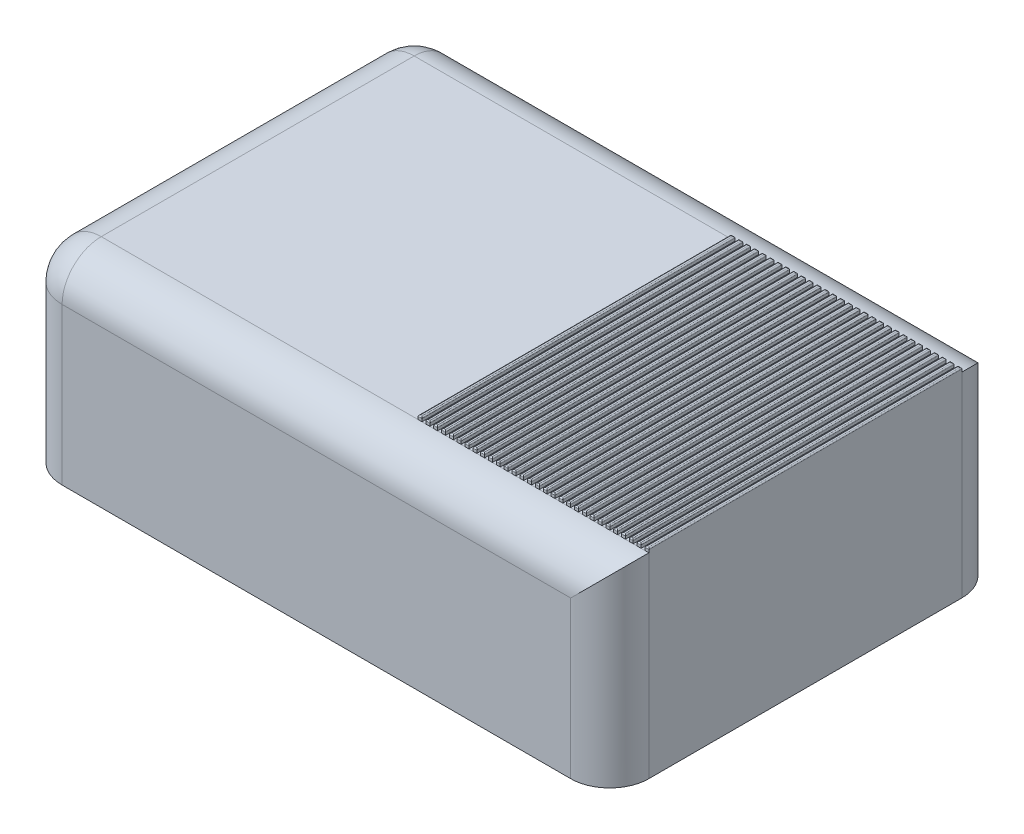
SolidWorks part; units mm, degrees
ref_plane "Front Plane" through (0, 0, 0) normal (0, 0, 1) x (1, 0, 0)
ref_plane "Top Plane" through (0, 0, 0) normal (0, 1, 0) x (1, 0, 0)
ref_plane "Right Plane" through (0, 0, 0) normal (1, 0, 0) x (0, 0, -1)
sketch "Sketch3" plane through (0, 0, 0) normal (0, 1, 0) x (1, 0, 0)
  line L1 (-37.5, -25) -> (37.5, -25)
  line L2 (-37.5, -25) -> (-37.5, 25)
  line L3 (-37.5, 25) -> (37.5, 25)
  line L4 (37.5, -25) -> (37.5, 25)
  line L5 (-37.5, -25) -> (37.5, 25) construction
  line L6 (-37.5, 25) -> (37.5, -25) construction
  point P0 (0, 0)
  dimension "D1" = 75
  dimension "D2" = 50
extrude "Boss-Extrude1" add sketch "Sketch3" along normal blind 25
sketch "Sketch4" plane through (0, 0, 0) normal (0, -1, 0) x (1, 0, 0)
  line L0 (37.5, 25) -> (37.5, -25) construction
  line L1 (7.5, -10) -> (17.5, -10)
  line L2 (7.5, -10) -> (7.5, 10)
  line L3 (7.5, 10) -> (17.5, 10)
  line L4 (17.5, -10) -> (17.5, 10)
  line L5 (7.5, -10) -> (17.5, 10) construction
  line L6 (7.5, 10) -> (17.5, -10) construction
  point P0 (12.5, 0)
  dimension "D1" = 10
  dimension "D2" = 20
  dimension "D3" = 20
extrude "Boss-Extrude2" add sketch "Sketch4" along normal blind 15 contours L1 L4 L3 L2 region at (12.5, 0, 0)
fillet "Fillet1" radius 5 2 edges at (7.5, -15, 0) (17.5, -15, 0)
sketch "Sketch5" plane through (0, 0, 10) normal (0, 0, 1) x (1, 0, 0)
  circle A0 centre (12.5, -10) radius 2.5
  arc A1 (12.5, -15) -> (17.5, -10) centre (12.5, -10) ccw construction
  dimension "D1" = 5
extrude "Cut-Extrude1" cut sketch "Sketch5" against normal through all
sketch "Sketch8" plane through (0, 0, 0) normal (0, -1, 0) x (-1, 0, 0)
  line L0 (-37.5, -25) -> (-37.5, 25) construction
  circle A0 centre (-27.5, 0) radius 2.75
  dimension "D1" = 5.5
  dimension "D2" = 10
extrude "Cut-Extrude2" cut sketch "Sketch8" against normal blind 5
sketch "Sketch9" plane through (0, 5, 0) normal (0, -1, 0) x (1, 0, 0)
  circle A0 centre (27.5, 0) radius 2.125
  dimension "D1" = 4.25
extrude "Boss-Extrude3" add sketch "Sketch9" along normal blind 10
ref_plane "Plane1" through (0, 2, 0) normal (0, -1, 0) x (-1, 0, 0)
sketch "Sketch10" plane through (0, 2, 0) normal (0, -1, 0) x (-1, 0, 0)
  line L0 (-27.5, 0) -> (-30.5, 0)
  line L1 (-27.5, 0) -> (-29, -2.5981)
  line L2 (-26.125, -2.3816) -> (-28.875, 2.3816) construction
  line L3 (-27.5, 0) -> (-29.8816, -1.375) construction
  line L4 (-27.5, 0) -> (-24.5, 0)
  line L5 (-27.5, 0) -> (-26, 2.5981)
  circle A0 centre (-27.5, 0) radius 2.25
  circle A2 centre (-27.5, 0) radius 2.75
  point P10 (-27.5, 0)
  dimension "D1" = 4.5
  dimension "D5" = 5.5
  dimension "D2" = 3
  dimension "D3" = 3
  dimension "D4" = 60
  dimension "D6" = 60
  dimension "D7" = 30
extrude "Boss-Extrude4" add sketch "Sketch10" along normal blind 0.75 contours L0 A2 L1 A0 | L4 A2 L5 A0 region at (29.5744, 2, 1.1976) region at (25.4256, 2, -1.1976)
fillet "Fillet2" radius 5 7 edges at (0, 25, 25) (-37.5, 25, 0) (0, 25, -25) (-37.5, 12.5, -25) (-37.5, 12.5, 25) (37.5, 12.5, -25) (37.5, 12.5, 25)
sketch "Sketch13" plane through (0, 25, 0) normal (0, 1, 0) x (1, 0, 0)
  line L0 (37.5, 20) -> (-32.5, 20) construction
  line L1 (37.5, -20) -> (37, -20)
  line L2 (37.5, -20) -> (37.5, 20)
  line L3 (37.5, 20) -> (37, 20)
  line L4 (37, -20) -> (37, 20)
  line L5 (36.5, 20) -> (36, 20)
  line L6 (36.5, -20) -> (36.5, 20)
  line L7 (36, -20) -> (36, 20)
  line L8 (36.5, -20) -> (36, -20)
  line L9 (35.5, 20) -> (35, 20)
  line L10 (35.5, -20) -> (35.5, 20)
  line L11 (35, -20) -> (35, 20)
  line L12 (35.5, -20) -> (35, -20)
  line L13 (34.5, 20) -> (34, 20)
  line L14 (34.5, -20) -> (34.5, 20)
  line L15 (34, -20) -> (34, 20)
  line L16 (34.5, -20) -> (34, -20)
  line L17 (33.5, 20) -> (33, 20)
  line L18 (33.5, -20) -> (33.5, 20)
  line L19 (33, -20) -> (33, 20)
  line L20 (33.5, -20) -> (33, -20)
  line L21 (32.5, 20) -> (32, 20)
  line L22 (32.5, -20) -> (32.5, 20)
  line L23 (32, -20) -> (32, 20)
  line L24 (32.5, -20) -> (32, -20)
  line L25 (31.5, 20) -> (31, 20)
  line L26 (31.5, -20) -> (31.5, 20)
  line L27 (31, -20) -> (31, 20)
  line L28 (31.5, -20) -> (31, -20)
  line L29 (30.5, 20) -> (30, 20)
  line L30 (30.5, -20) -> (30.5, 20)
  line L31 (30, -20) -> (30, 20)
  line L32 (30.5, -20) -> (30, -20)
  line L33 (29.5, 20) -> (29, 20)
  line L34 (29.5, -20) -> (29.5, 20)
  line L35 (29, -20) -> (29, 20)
  line L36 (29.5, -20) -> (29, -20)
  line L37 (28.5, 20) -> (28, 20)
  line L38 (28.5, -20) -> (28.5, 20)
  line L39 (28, -20) -> (28, 20)
  line L40 (28.5, -20) -> (28, -20)
  line L41 (27.5, 20) -> (27, 20)
  line L42 (27.5, -20) -> (27.5, 20)
  line L43 (27, -20) -> (27, 20)
  line L44 (27.5, -20) -> (27, -20)
  line L45 (26.5, 20) -> (26, 20)
  line L46 (26.5, -20) -> (26.5, 20)
  line L47 (26, -20) -> (26, 20)
  line L48 (26.5, -20) -> (26, -20)
  line L49 (25.5, 20) -> (25, 20)
  line L50 (25.5, -20) -> (25.5, 20)
  line L51 (25, -20) -> (25, 20)
  line L52 (25.5, -20) -> (25, -20)
  line L53 (24.5, 20) -> (24, 20)
  line L54 (24.5, -20) -> (24.5, 20)
  line L55 (24, -20) -> (24, 20)
  line L56 (24.5, -20) -> (24, -20)
  line L57 (23.5, 20) -> (23, 20)
  line L58 (23.5, -20) -> (23.5, 20)
  line L59 (23, -20) -> (23, 20)
  line L60 (23.5, -20) -> (23, -20)
  line L61 (22.5, 20) -> (22, 20)
  line L62 (22.5, -20) -> (22.5, 20)
  line L63 (22, -20) -> (22, 20)
  line L64 (22.5, -20) -> (22, -20)
  line L65 (21.5, 20) -> (21, 20)
  line L66 (21.5, -20) -> (21.5, 20)
  line L67 (21, -20) -> (21, 20)
  line L68 (21.5, -20) -> (21, -20)
  line L69 (20.5, 20) -> (20, 20)
  line L70 (20.5, -20) -> (20.5, 20)
  line L71 (20, -20) -> (20, 20)
  line L72 (20.5, -20) -> (20, -20)
  line L73 (19.5, 20) -> (19, 20)
  line L74 (19.5, -20) -> (19.5, 20)
  line L75 (19, -20) -> (19, 20)
  line L76 (19.5, -20) -> (19, -20)
  line L77 (18.5, 20) -> (18, 20)
  line L78 (18.5, -20) -> (18.5, 20)
  line L79 (18, -20) -> (18, 20)
  line L80 (18.5, -20) -> (18, -20)
  line L81 (17.5, 20) -> (17, 20)
  line L82 (17.5, -20) -> (17.5, 20)
  line L83 (17, -20) -> (17, 20)
  line L84 (17.5, -20) -> (17, -20)
  line L85 (16.5, 20) -> (16, 20)
  line L86 (16.5, -20) -> (16.5, 20)
  line L87 (16, -20) -> (16, 20)
  line L88 (16.5, -20) -> (16, -20)
  line L89 (15.5, 20) -> (15, 20)
  line L90 (15.5, -20) -> (15.5, 20)
  line L91 (15, -20) -> (15, 20)
  line L92 (15.5, -20) -> (15, -20)
  line L93 (14.5, 20) -> (14, 20)
  line L94 (14.5, -20) -> (14.5, 20)
  line L95 (14, -20) -> (14, 20)
  line L96 (14.5, -20) -> (14, -20)
  line L97 (13.5, 20) -> (13, 20)
  line L98 (13.5, -20) -> (13.5, 20)
  line L99 (13, -20) -> (13, 20)
  line L100 (13.5, -20) -> (13, -20)
  line L101 (12.5, 20) -> (12, 20)
  line L102 (12.5, -20) -> (12.5, 20)
  line L103 (12, -20) -> (12, 20)
  line L104 (12.5, -20) -> (12, -20)
  line L105 (11.5, 20) -> (11, 20)
  line L106 (11.5, -20) -> (11.5, 20)
  line L107 (11, -20) -> (11, 20)
  line L108 (11.5, -20) -> (11, -20)
  line L109 (10.5, 20) -> (10, 20)
  line L110 (10.5, -20) -> (10.5, 20)
  line L111 (10, -20) -> (10, 20)
  line L112 (10.5, -20) -> (10, -20)
  line L113 (9.5, 20) -> (9, 20)
  line L114 (9.5, -20) -> (9.5, 20)
  line L115 (9, -20) -> (9, 20)
  line L116 (9.5, -20) -> (9, -20)
  line L117 (8.5, 20) -> (8, 20)
  line L118 (8.5, -20) -> (8.5, 20)
  line L119 (8, -20) -> (8, 20)
  line L120 (8.5, -20) -> (8, -20)
  line L121 (37.5, 20) -> (36.5, 20) construction
  dimension "D1" = 0.5
  dimension "D3" = 1
  dimension "D2" = 30
extrude "Boss-Extrude5" add sketch "Sketch13" along normal blind 0.5
fillet "Fillet3" radius 0.15 120 edges at (37.25, 25.5, 20) (37, 25.5, 0) (37.25, 25.5, -20) (37.5, 25.5, 0) (36, 25.5, 0) (36.25, 25.5, -20) (36.5, 25.5, 0) (36.25, 25.5, 20) (35, 25.5, 0) (35.25, 25.5, -20) (35.5, 25.5, 0) (35.25, 25.5, 20) (34, 25.5, 0) (34.25, 25.5, -20) (34.5, 25.5, 0) (34.25, 25.5, 20) (33, 25.5, 0) (33.25, 25.5, -20) (33.5, 25.5, 0) (33.25, 25.5, 20) (32, 25.5, 0) (32.25, 25.5, -20) (32.5, 25.5, 0) (32.25, 25.5, 20) (31, 25.5, 0) (31.25, 25.5, -20) (31.5, 25.5, 0) (31.25, 25.5, 20) (30, 25.5, 0) (30.25, 25.5, -20) (30.5, 25.5, 0) (30.25, 25.5, 20) (29, 25.5, 0) (29.25, 25.5, -20) (29.5, 25.5, 0) (29.25, 25.5, 20) (28, 25.5, 0) (28.25, 25.5, -20) (28.5, 25.5, 0) (28.25, 25.5, 20) (27, 25.5, 0) (27.25, 25.5, -20) (27.5, 25.5, 0) (27.25, 25.5, 20) (26, 25.5, 0) (26.25, 25.5, -20) (26.5, 25.5, 0) (26.25, 25.5, 20) (25, 25.5, 0) (25.25, 25.5, -20) (25.5, 25.5, 0) (25.25, 25.5, 20) (24, 25.5, 0) (24.25, 25.5, -20) (24.5, 25.5, 0) (24.25, 25.5, 20) (23, 25.5, 0) (23.25, 25.5, -20) (23.5, 25.5, 0) (23.25, 25.5, 20) (22, 25.5, 0) (22.25, 25.5, -20) (22.5, 25.5, 0) (22.25, 25.5, 20) (21, 25.5, 0) (21.25, 25.5, -20) (21.5, 25.5, 0) (21.25, 25.5, 20) (20, 25.5, 0) (20.25, 25.5, -20) (20.5, 25.5, 0) (20.25, 25.5, 20) (19, 25.5, 0) (19.25, 25.5, -20) (19.5, 25.5, 0) (19.25, 25.5, 20) (18, 25.5, 0) (18.25, 25.5, -20) (18.5, 25.5, 0) (18.25, 25.5, 20) (17, 25.5, 0) (17.25, 25.5, -20) (17.5, 25.5, 0) (17.25, 25.5, 20) (16, 25.5, 0) (16.25, 25.5, -20) (16.5, 25.5, 0) (16.25, 25.5, 20) (15, 25.5, 0) (15.25, 25.5, -20) (15.5, 25.5, 0) (15.25, 25.5, 20) (14, 25.5, 0) (14.25, 25.5, -20) (14.5, 25.5, 0) (14.25, 25.5, 20) (13, 25.5, 0) (13.25, 25.5, -20) (13.5, 25.5, 0) (13.25, 25.5, 20) (12, 25.5, 0) (12.25, 25.5, -20) (12.5, 25.5, 0) (12.25, 25.5, 20) (11, 25.5, 0) (11.25, 25.5, -20) (11.5, 25.5, 0) (11.25, 25.5, 20) (10, 25.5, 0) (10.25, 25.5, -20) (10.5, 25.5, 0) (10.25, 25.5, 20) (9, 25.5, 0) (9.25, 25.5, -20) (9.5, 25.5, 0) (9.25, 25.5, 20) (8, 25.5, 0) (8.25, 25.5, -20) (8.5, 25.5, 0) (8.25, 25.5, 20)
sketch "Sketch14" plane through (0, 0, 0) normal (0, -1, 0) x (1, 0, 0)
  line L0 (-37.5, -20) -> (-37.5, 20) construction
  line L1 (-25.5, -7.5) -> (-20.5, -7.5)
  line L2 (-25.5, -7.5) -> (-25.5, 7.5)
  line L3 (-25.5, 7.5) -> (-20.5, 7.5)
  line L4 (-20.5, -7.5) -> (-20.5, 7.5)
  line L5 (-25.5, -7.5) -> (-20.5, 7.5) construction
  line L6 (-25.5, 7.5) -> (-20.5, -7.5) construction
  point P0 (-23, 0)
  point P7 (-37.5, 0)
  point P8 (0, 0)
  dimension "D1" = 12
  dimension "D2" = 5
  dimension "D3" = 15
extrude "Boss-Extrude6" add sketch "Sketch14" along normal blind 8
fillet "Fillet4" radius 2 6 edges at (-23, -8, -7.5) (-20.5, -4, -7.5) (-23, -8, 7.5) (-20.5, -4, 7.5) (-25.5, -4, 7.5) (-25.5, -4, -7.5)
sketch "Sketch15" plane through (-25.5, 0, 0) normal (-1, 0, 0) x (0, 0, 1)
  line L0 (5.5, -8) -> (-5.5, -8) construction
  circle A0 centre (0, -8) radius 4
  dimension "D1" = 8
extrude "Cut-Extrude3" cut sketch "Sketch15" against normal blind 10
fillet "Fillet5" radius 2 2 edges at (-23, -8, -4) (-23, -8, 4)
